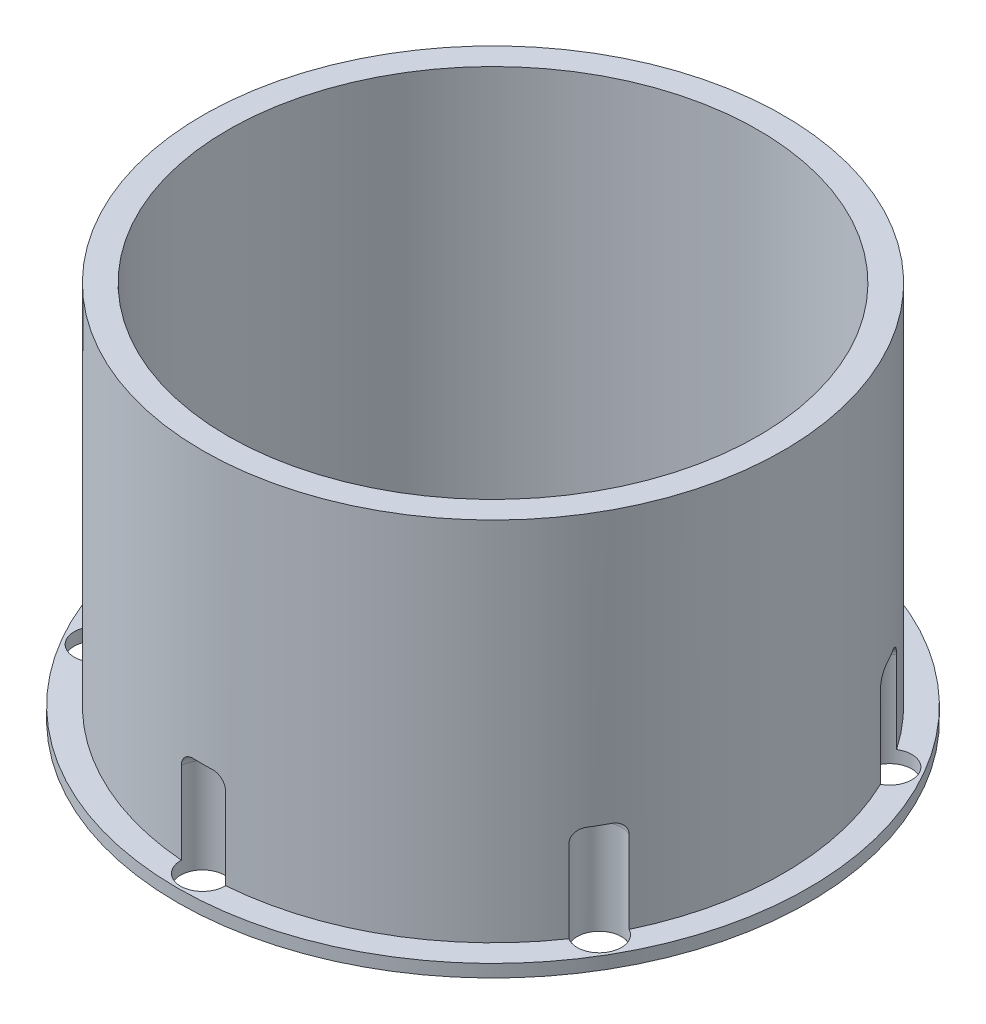
SolidWorks part; units mm, degrees
ref_plane "Front Plane" through (0, 0, 0) normal (0, 0, 1) x (1, 0, 0)
ref_plane "Top Plane" through (0, 0, 0) normal (0, 1, 0) x (1, 0, 0)
ref_plane "Right Plane" through (0, 0, 0) normal (1, 0, 0) x (0, 0, -1)
sketch "Sketch4" plane through (0, 0, 0) normal (0, 1, 0) x (1, 0, 0)
  circle A0 centre (0, 0) radius 53.34
  circle A1 centre (0, 0) radius 63.5
  dimension "D1" = 106.68
  dimension "D2" = 127
extrude "Boss-Extrude1" add sketch "Sketch4" along normal blind 2.54
sketch "Sketch6" plane through (0, 2.54, 0) normal (0, 1, 0) x (1, 0, 0)
  line L0 (0, -53.34) -> (0, -63.5) construction
  circle A0 centre (0, 0) radius 53.34 construction
  circle A1 centre (0, 0) radius 63.5 construction
  circle A2 centre (0, -58.42) radius 4.445
  dimension "D1" = 8.89
extrude "Cut-Extrude2" cut sketch "Sketch6" against normal blind 2.54
pattern_circular "CirPattern1" count 6 over 360 about axis through (0, 2.54, 0) along (0, 1, 0) of "Cut-Extrude2"
sketch "Sketch9" plane through (0, 2.54, 0) normal (0, 1, 0) x (1, 0, 0)
  circle A0 centre (0, 0) radius 58.42
  circle A1 centre (0, 0) radius 53.34
  dimension "D1" = 106.68
extrude "Boss-Extrude2" add sketch "Sketch9" along normal blind 73.66
extrude "Cut-Extrude3" cut sketch "Sketch6<2>" along normal blind 19.05
sketch "Sketch6<2>" plane through (0, 2.54, 0) normal (0, 1, 0) x (1, 0, 0) same geometry as "Sketch6"
fillet "Fillet1" radius 2.54 1 edges at (0, 21.59, 53.975)
pattern_circular "CirPattern3" count 6 over 360 about axis through (0, 76.2, 0) along (0, -1, 0) of "Fillet1", "Cut-Extrude3"
ref_plane "Plane6" through (68.58, 0, 0) normal (1, 0, 0) x (0, 0, -1)
